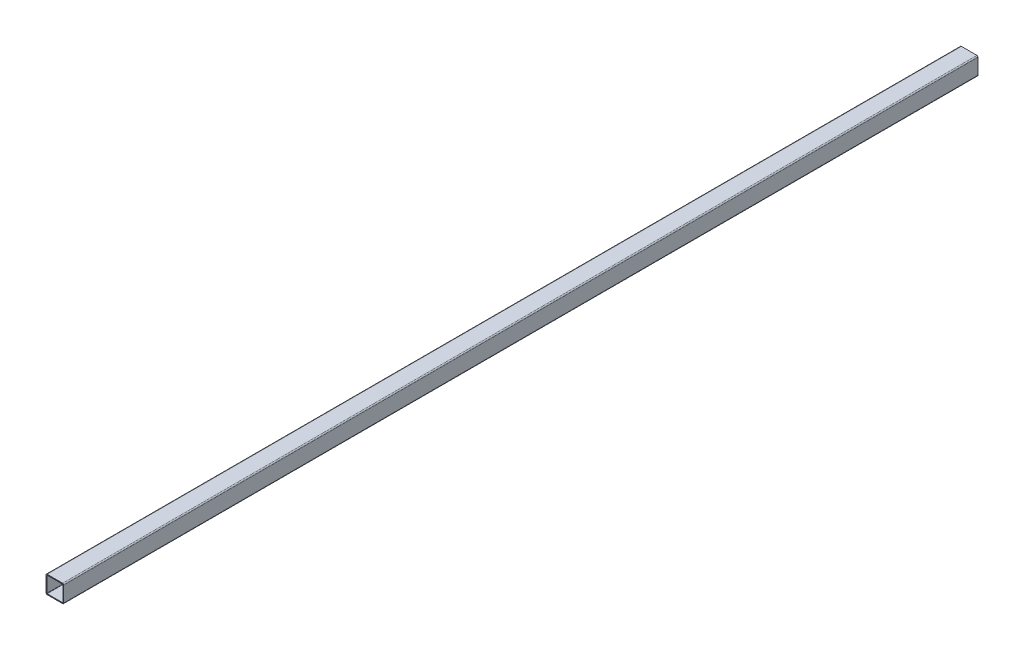
SolidWorks part; units mm, degrees
material "AISI 1010 Steel, hot rolled bar"
ref_plane "Front Plane" through (0, 0, 0) normal (0, 0, 1) x (1, 0, 0)
ref_plane "Top Plane" through (0, 0, 0) normal (0, 1, 0) x (1, 0, 0)
ref_plane "Right Plane" through (0, 0, 0) normal (1, 0, 0) x (0, 0, -1)
sketch "Sketch1" plane through (0, 0, 0) normal (0, 0, 1) x (1, 0, 0)
  line L0 (-14, 14.48) -> (14, 14.48)
  line L1 (-14, -16) -> (14, -16)
  line L2 (-16, -14) -> (-16, 14)
  line L3 (-14, 16) -> (14, 16)
  line L4 (16, -14) -> (16, 14)
  line L5 (-16, -16) -> (16, 16) construction
  line L6 (-16, 16) -> (16, -16) construction
  line L7 (14.48, -14) -> (14.48, 14)
  line L8 (-14, -14.48) -> (14, -14.48)
  line L9 (-14.48, -14) -> (-14.48, 14)
  arc A0 (14, -16) -> (16, -14) centre (14, -14) ccw
  arc A1 (-16, 14) -> (-14, 16) centre (-14, 14) cw
  arc A2 (-16, -14) -> (-14, -16) centre (-14, -14) ccw
  arc A3 (16, 14) -> (14, 16) centre (14, 14) ccw
  arc A4 (14.48, 14) -> (14, 14.48) centre (14, 14) ccw
  arc A5 (14, -14.48) -> (14.48, -14) centre (14, -14) ccw
  arc A6 (-14.48, -14) -> (-14, -14.48) centre (-14, -14) ccw
  arc A7 (-14.48, 14) -> (-14, 14.48) centre (-14, 14) cw
  point P0 (0, 0)
  dimension "D3" = 2
  dimension "D1" = 32
  dimension "D2" = 32
  dimension "D4" = 1.52
extrude "Boss-Extrude1" add sketch "Sketch1" along normal blind 825 and the other way blind 825
